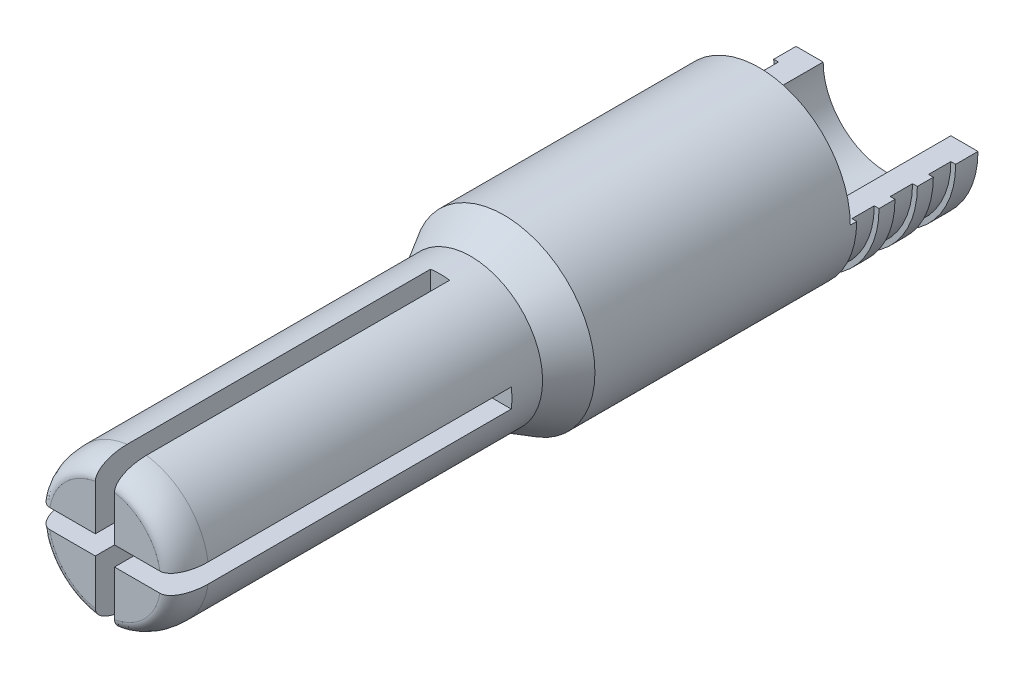
SolidWorks part; units mm, degrees
material "Латунь"
ref_plane "Спереди" through (0, 0, 0) normal (0, 0, 1) x (1, 0, 0)
ref_plane "Сверху" through (0, 0, 0) normal (0, 1, 0) x (1, 0, 0)
ref_plane "Справа" through (0, 0, 0) normal (1, 0, 0) x (0, 0, -1)
sketch "Эскиз1" plane through (0, 0, 0) normal (0, 0, 1) x (1, 0, 0)
  circle A0 centre (0, 0) radius 2.85
  dimension "D1" = 5.7
extrude "Бобышка-Вытянуть1" add sketch "Эскиз1" along normal blind 12
sketch "Эскиз2" plane through (0, 0, 12) normal (0, 0, 1) x (1, 0, 0)
  circle A0 centre (0, 0) radius 2.25
  dimension "D1" = 4.5
extrude "Бобышка-Вытянуть2" add sketch "Эскиз2" along normal blind 12.5
sketch "Эскиз3" plane through (0, 0, 0) normal (0, 0, -1) x (-1, 0, 0)
  circle A0 centre (0, 0) radius 2
  dimension "D1" = 4
extrude "Вырез-Вытянуть1" cut sketch "Эскиз3" against normal blind 12
chamfer "Фаска1" distance 1.5 angle 20 1 edges at (-2, 0, 12) first distance on face at (-2, 0, 12)
sketch "Эскиз4" plane through (0, 0, 0) normal (1, 0, 0) x (0, 0, -1)
  line L0 (0, -2.85) -> (0, 2.85) construction
  line L1 (2.3755, 4.1937) -> (-4, 4.1937)
  line L2 (2.3755, 4.1937) -> (2.3755, 0)
  line L3 (2.3755, 0) -> (-4, 0)
  line L4 (-4, 4.1937) -> (-4, 0)
  dimension "D1" = 4.1937
  dimension "D2" = 6.3755
  dimension "D3" = 4
extrude "Вырез-Вытянуть2" cut sketch "Эскиз4" against normal through all both and the other way through all
sketch "Эскиз5" plane through (0, 0, 0) normal (1, 0, 0) x (0, 0, -1)
  line L0 (0, 0) -> (-8.7729, 0) construction
  line L1 (-12, -2.85) -> (0, -2.85) construction
  line L2 (-1.4, -2.7) -> (-0.7, -2.7)
  line L3 (-1.4, -2.7) -> (-1.4, -3)
  line L4 (-1.4, -3) -> (-0.7, -3)
  line L5 (-0.7, -2.7) -> (-0.7, -3)
  line L6 (-1.05, -3) -> (-1.05, -2.7) construction
  line L7 (-1.4, -2.85) -> (-0.7, -2.85) construction
  line L8 (0, -2.85) -> (0, 0) construction
  line L9 (-2.6, -2.7) -> (-2.6, -3)
  line L10 (-2.6, -2.7) -> (-1.9, -2.7)
  line L11 (-1.9, -2.7) -> (-1.9, -3)
  line L12 (-2.6, -3) -> (-1.9, -3)
  line L13 (-3.8, -2.7) -> (-3.8, -3)
  line L14 (-3.8, -2.7) -> (-3.1, -2.7)
  line L15 (-3.1, -2.7) -> (-3.1, -3)
  line L16 (-3.8, -3) -> (-3.1, -3)
  point P3 (-1.05, -2.85)
  dimension "D1" = 0.3
  dimension "D2" = 0.7
  dimension "D3" = 0.7
  dimension "D4" = 3
revolve "Вырез-Повернуть1" cut sketch "Эскиз5" angle 360 about L0 region at (0, -2.85, 2.25) region at (0, -2.85, 3.45)
chamfer "Фаска2" distance 0.6 angle 60 1 edges at (2.25, 0, 12) first distance on face at (2.25, 0, 12)
sketch "Эскиз6" plane through (0, 0, 24.5) normal (0, 0, 1) x (1, 0, 0)
  line L1 (-0.3, -2.5) -> (0.3, -2.5)
  line L2 (-0.3, -2.5) -> (-0.3, 2.5)
  line L3 (-0.3, 2.5) -> (0.3, 2.5)
  line L4 (0.3, -2.5) -> (0.3, 2.5)
  line L5 (0, 2.5) -> (0, -2.5) construction
  line L6 (-0.3, 0) -> (0.3, 0) construction
  line L7 (-2.5, 0.3) -> (2.5, 0.3)
  line L8 (-2.5, 0.3) -> (-2.5, -0.3)
  line L9 (-2.5, -0.3) -> (2.5, -0.3)
  line L10 (2.5, 0.3) -> (2.5, -0.3)
  line L11 (0, -0.3) -> (0, 0.3) construction
  line L12 (-2.5, 0) -> (2.5, 0) construction
  point P0 (0, 0)
  point P4 (0, 0)
  dimension "D1" = 5
  dimension "D2" = 0.6
  dimension "D3" = 0.6
  dimension "D4" = 5
extrude "Вырез-Вытянуть3" cut sketch "Эскиз6" against normal blind 10.5 contours L2 L1 L4 L3 | L8 L7 L10 L9
fillet "Скругление1" radius 1 4 edges at (-1.591, 1.591, 24.5) (-1.591, -1.591, 24.5) (1.591, -1.591, 24.5) (1.591, 1.591, 24.5) second distance 0.5 first distance on face at (0, 0, 19.25)
